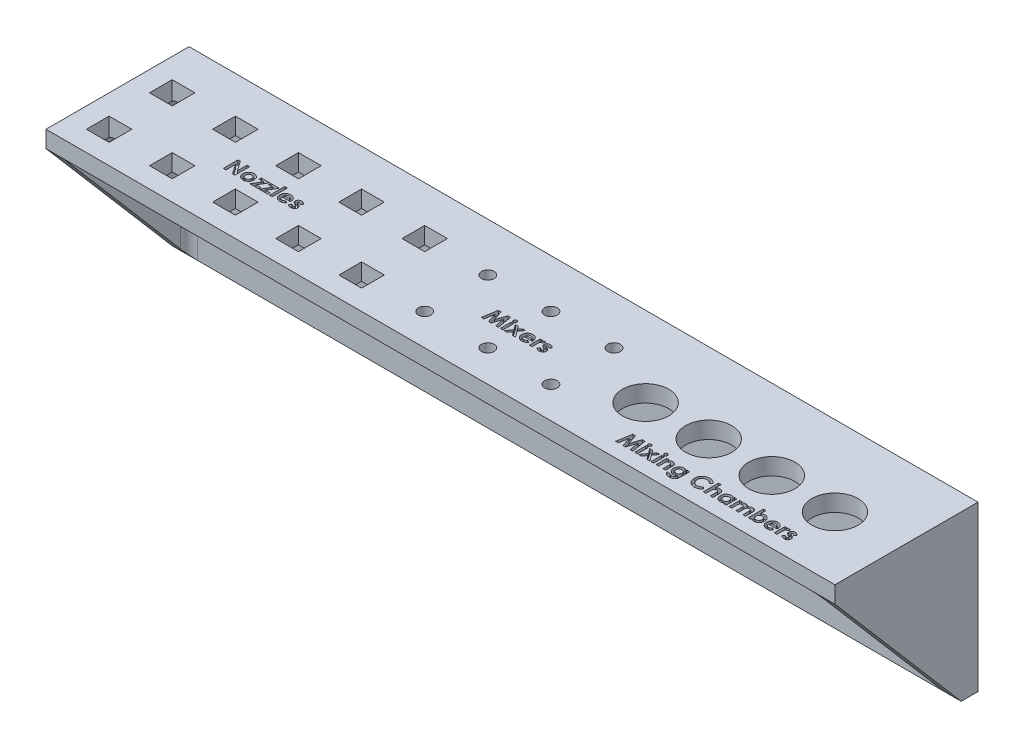
SolidWorks part; units mm, degrees
ref_plane "Front Plane" through (0, 0, 0) normal (0, 0, 1) x (1, 0, 0)
ref_plane "Top Plane" through (0, 0, 0) normal (0, 1, 0) x (1, 0, 0)
ref_plane "Right Plane" through (0, 0, 0) normal (1, 0, 0) x (0, 0, -1)
sketch "Sketch1" plane through (0, 0, 0) normal (0, 1, 0) x (1, 0, 0)
  line L0 (19.8, 4.8) -> (19.8, 10.2)
  line L1 (4.8, 4.8) -> (10.2, 4.8)
  line L2 (4.8, 4.8) -> (4.8, 10.2)
  line L3 (4.8, 10.2) -> (10.2, 10.2)
  line L4 (10.2, 4.8) -> (10.2, 10.2)
  line L5 (4.8, 4.8) -> (10.2, 10.2) construction
  line L6 (4.8, 10.2) -> (10.2, 4.8) construction
  line L7 (0, 0) -> (187.5, 0)
  line L8 (0, 0) -> (0, 30)
  line L9 (0, 30) -> (187.5, 30)
  line L10 (187.5, 0) -> (187.5, 30)
  line L11 (19.8, 4.8) -> (25.2, 4.8)
  line L12 (25.2, 4.8) -> (25.2, 10.2)
  line L13 (19.8, 10.2) -> (25.2, 10.2)
  line L14 (34.8, 4.8) -> (34.8, 10.2)
  line L15 (34.8, 4.8) -> (40.2, 4.8)
  line L16 (40.2, 4.8) -> (40.2, 10.2)
  line L17 (34.8, 10.2) -> (40.2, 10.2)
  line L18 (49.8, 4.8) -> (49.8, 10.2)
  line L19 (49.8, 4.8) -> (55.2, 4.8)
  line L20 (55.2, 4.8) -> (55.2, 10.2)
  line L21 (49.8, 10.2) -> (55.2, 10.2)
  line L22 (64.8, 4.8) -> (64.8, 10.2)
  line L23 (64.8, 4.8) -> (70.2, 4.8)
  line L24 (70.2, 4.8) -> (70.2, 10.2)
  line L25 (64.8, 10.2) -> (70.2, 10.2)
  line L26 (19.8, 19.8) -> (19.8, 25.2)
  line L27 (19.8, 19.8) -> (25.2, 19.8)
  line L28 (25.2, 19.8) -> (25.2, 25.2)
  line L29 (19.8, 25.2) -> (25.2, 25.2)
  line L30 (34.8, 19.8) -> (34.8, 25.2)
  line L31 (34.8, 19.8) -> (40.2, 19.8)
  line L32 (40.2, 19.8) -> (40.2, 25.2)
  line L33 (34.8, 25.2) -> (40.2, 25.2)
  line L34 (49.8, 19.8) -> (49.8, 25.2)
  line L35 (49.8, 19.8) -> (55.2, 19.8)
  line L36 (55.2, 19.8) -> (55.2, 25.2)
  line L37 (49.8, 25.2) -> (55.2, 25.2)
  line L38 (64.8, 19.8) -> (64.8, 25.2)
  line L39 (64.8, 19.8) -> (70.2, 19.8)
  line L40 (70.2, 19.8) -> (70.2, 25.2)
  line L41 (64.8, 25.2) -> (70.2, 25.2)
  line L42 (4.8, 19.8) -> (4.8, 25.2)
  line L43 (4.8, 19.8) -> (10.2, 19.8)
  line L44 (10.2, 19.8) -> (10.2, 25.2)
  line L45 (4.8, 25.2) -> (10.2, 25.2)
  line L46 (4.8, 4.8) -> (19.8, 4.8) construction
  line L47 (4.8, 4.8) -> (4.8, 19.8) construction
  line L54 (0, 15) -> (187.5, 15) construction
  line L62 (82.5, 7.5) -> (97.5, 7.5) construction
  line L112 (127.5, 15) -> (142.5, 15) construction
  circle A0 centre (7.5, 7.5) radius 3.35 construction
  circle A17 centre (82.5, 7.5) radius 1.5
  circle A18 centre (97.5, 7.5) radius 1.5
  circle A19 centre (112.5, 7.5) radius 1.5
  circle A20 centre (97.5, 22.5) radius 1.5
  circle A21 centre (112.5, 22.5) radius 1.5
  circle A22 centre (82.5, 22.5) radius 1.5
  circle A23 centre (127.5, 15) radius 5.5
  circle A24 centre (142.5, 15) radius 5.5
  circle A25 centre (157.5, 15) radius 5.5
  circle A26 centre (172.5, 15) radius 5.5
  point P2 (7.5, 7.5)
  point P56 (70.2, 22.5)
  point P57 (437.5682, 7.5)
  point P142 (135.0079, 7.5)
  point P162 (79.6469, 7.5)
  point P163 (67.5, 4.8)
  dimension "D2" = 6.7
  dimension "D37" = 3
  dimension "D44" = 11
  dimension "D1" = 5.4
  dimension "D5" = 15
  dimension "D6" = 15
  dimension "D7" = 7.5
  dimension "D8" = 7.5
  dimension "D9" = 30
  dimension "D11" = 15
  dimension "D40" = 15
  dimension "D41" = 7.5
  dimension "D43" = 15
  dimension "D45" = 15
  dimension "D47" = 15
  dimension "D48" = 15
  dimension "D3" = 5
  dimension "D4" = 2
  dimension "D38" = 3
  dimension "D39" = 2
  dimension "D46" = 4
extrude "Boss-Extrude1" add sketch "Sketch1" along normal blind 4
sketch "Sketch7" plane through (0, 4, 0) normal (0, 1, 0) x (1, 0, 0)
  line L0 (1.7059, 13) -> (116.5348, 13) construction
  line L1 (0, 0) -> (187.5, 0) construction
  text T0 "<b>Nozzles</b>"
  text T1 "<b>Mixers</b>"
  text T2 "<b>Mixing Chambers</b>"
  point P5 (0, 0)
  point P6 (0, 0)
  dimension "D1" = 13
extrude "Cut-Extrude1" cut sketch "Sketch7" against normal blind 1
sketch "Sketch2" plane through (0, 4, 0) normal (0, 1, 0) x (1, 0, 0)
  line L0 (187.5, 30) -> (0, 30) construction
  line L1 (187.5, 30) -> (0, 30)
extrude "Extrude-Thin1" add sketch "Sketch2" against normal blind 39 thin thin type one direction wall 4
sketch "Sketch3" plane through (187.5, 0, 0) normal (1, 0, 0) x (0, 0, -1)
  line L0 (0, 0) -> (30, -35)
rib "Rib1" sketch "Sketch3" sketch "Sketch3" thickness 4 extrusion direction parallel to sketch draft on no parameters "D1"=4
sketch "Sketch4" plane through (0, 0, 0) normal (-1, 0, 0) x (0, 0, 1)
  line L0 (-30, -35) -> (0, 0)
rib "Rib2" sketch "Sketch4" sketch "Sketch4" thickness 4 extrusion direction parallel to sketch draft on no parameters "D1"=4
hole_wizard "Ø4.0 (4) Diameter Hole1" positions "Sketch5" profile "Sketch6" hole size "Ø4.0" standard "ANSI Metric" end condition through all
sketch "Sketch5" plane through (0, 0, -30) normal (0, 0, 1) x (1, 0, 0)
  line L0 (4, -17.5) -> (183.5, -17.5) construction
  line L1 (4, -35) -> (4, 0) construction
  line L2 (183.5, 0) -> (183.5, -35) construction
  line L3 (0, -35) -> (0, 0) construction
  line L4 (187.5, 0) -> (187.5, -35) construction
  point P0 (20, -17.5)
  point P2 (167.5, -17.5)
  point P12 (13.3547, -17.5)
  point P13 (167.8552, -17.5)
  dimension "D1" = 20
  dimension "D2" = 20
sketch "Sketch6" plane through (20, -17.5, -30) normal (1, 0, 0) x (0, -1, 0)
  line L0 (0, 0) -> (0, 4)
  line L1 (0, 4) -> (2, 4)
  line L2 (2, 4) -> (2, 0)
  line L5 (2, 0) -> (0, 0)
  line L11 (0, -6.35) -> (0, 107.95) construction
  dimension "Thru Hole Dia." = 4
  dimension "Thru Hole Depth" = 4
fillet "Fillet1" radius 2 5 edges at (183.5, 0, -15) (183.5, -17.5, -30) (93.75, 0, -30) (4, -17.5, -30) (4, 0, -15)
